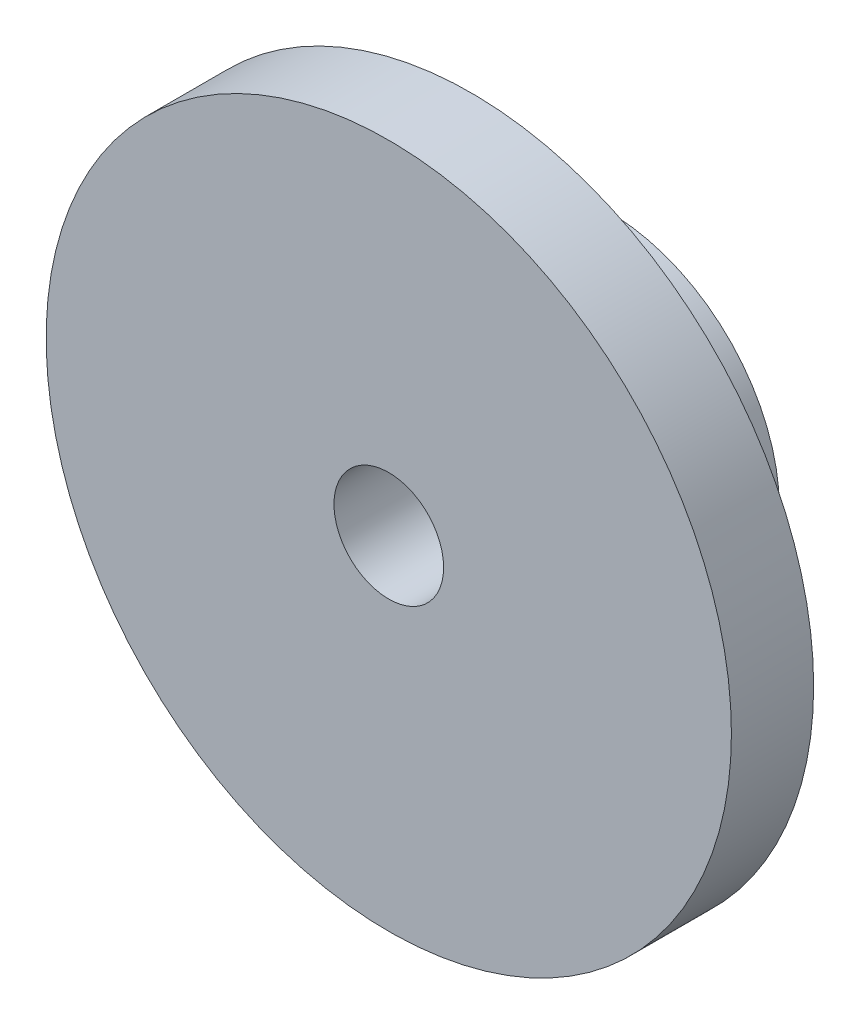
SolidWorks part; units mm, degrees
ref_plane "Front" through (0, 0, 0) normal (0, 0, 1) x (1, 0, 0)
ref_plane "Top" through (0, 0, 0) normal (0, 1, 0) x (1, 0, 0)
ref_plane "Right" through (0, 0, 0) normal (1, 0, 0) x (0, 0, -1)
sketch "Эскиз1" plane through (0, 0, 0) normal (0, 0, 1) x (1, 0, 0)
  circle A0 centre (0, 0) radius 12.5
  circle A1 centre (0, 0) radius 25
  circle A2 centre (0, 0) radius 4
  dimension "D1" = 50
  dimension "D2" = 25
  dimension "D3" = 8
extrude "Бобышка-Вытянуть1" add sketch "Эскиз1" along normal blind 6 contours A1 A0 | A0 A2 region at (-12.1464, 0, 0) region at (-24.2929, 0, 0)
extrude "Бобышка-Вытянуть2" add sketch "Эскиз1<3>" against normal blind 10 contours A0 A2 region at (-12.1464, 0, 0)
sketch "Эскиз1<3>" plane through (0, 0, 0) normal (0, 0, 1) x (1, 0, 0) same geometry as "Эскиз1"
